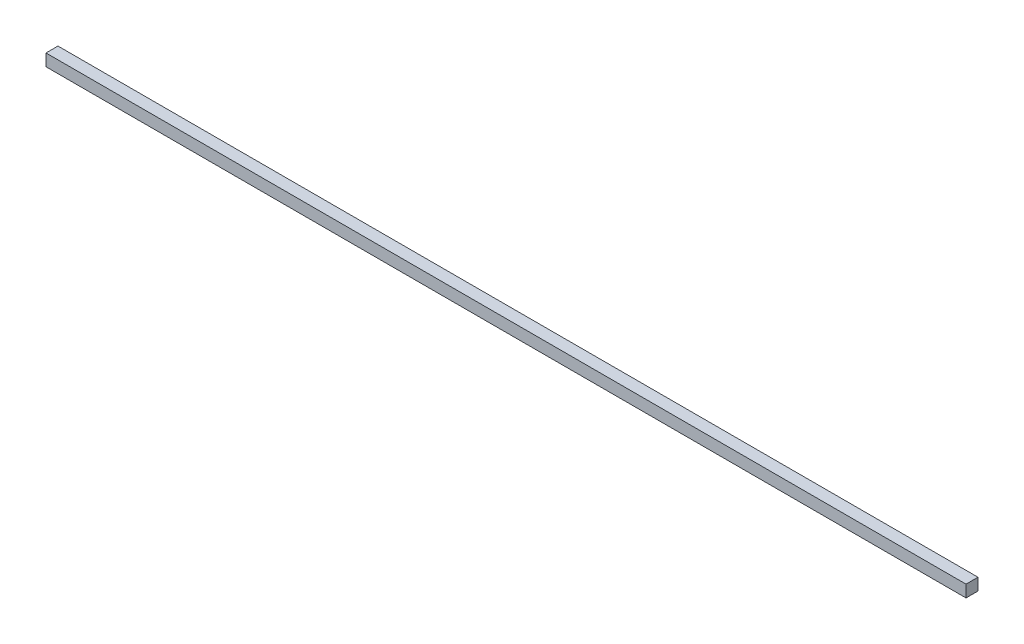
SolidWorks part; units mm, degrees
ref_plane "正面" through (0, 0, 0) normal (0, 0, 1) x (1, 0, 0)
ref_plane "平面" through (0, 0, 0) normal (0, 1, 0) x (1, 0, 0)
ref_plane "右側面" through (0, 0, 0) normal (1, 0, 0) x (0, 0, -1)
sketch "ｽｹｯﾁ1" plane through (0, 0, 0) normal (0, 0, 1) x (1, 0, 0)
  line L1 (-82.1516, 9.9786) -> (301.8484, 9.9786)
  line L2 (-82.1516, 9.9786) -> (-82.1516, 4.9786)
  line L3 (-82.1516, 4.9786) -> (301.8484, 4.9786)
  line L4 (301.8484, 9.9786) -> (301.8484, 4.9786)
  dimension "D3" = 5
  dimension "D4" = 384
extrude "ﾎﾞｽ - 押し出し1" add sketch "ｽｹｯﾁ1" along normal blind 5
